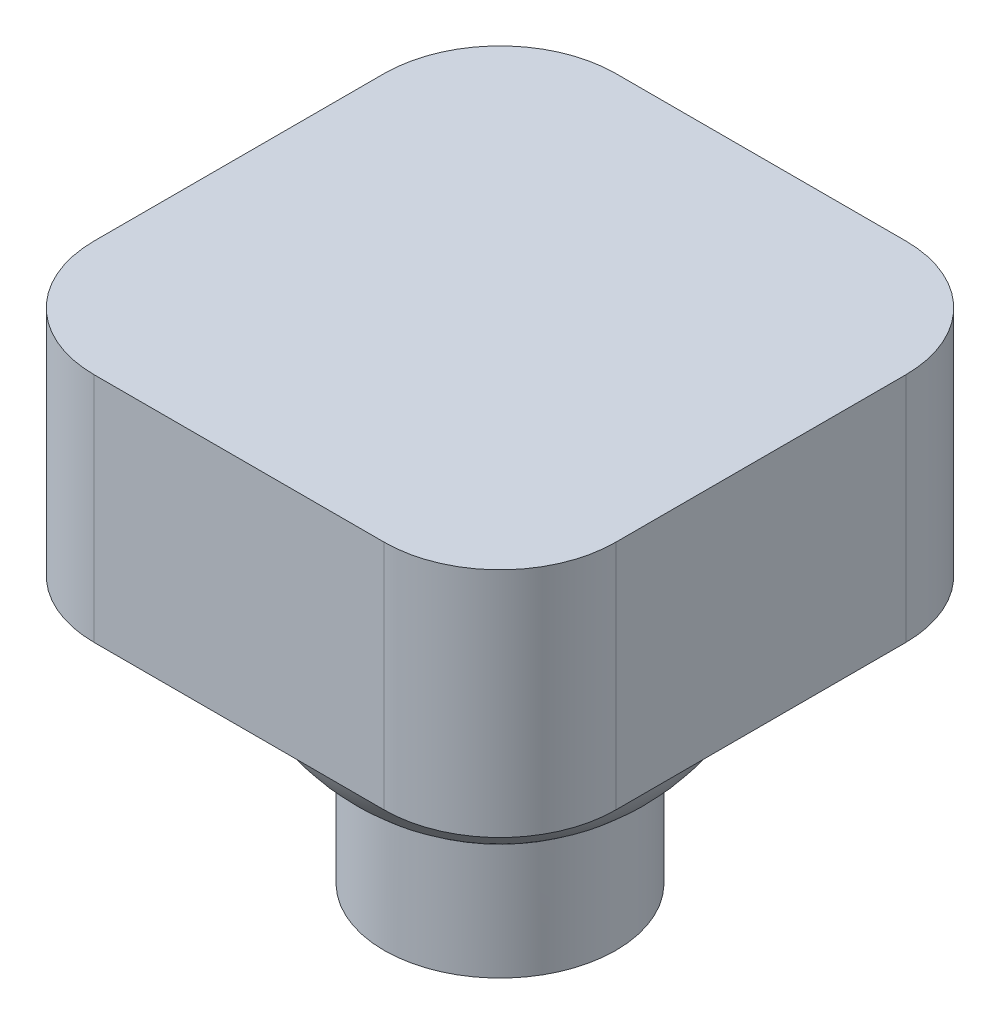
SolidWorks part; units mm, degrees
material "AISI 4340 Steel, normalized"
ref_plane "Front Plane" through (0, 0, 0) normal (0, 0, 1) x (1, 0, 0)
ref_plane "Top Plane" through (0, 0, 0) normal (0, 1, 0) x (1, 0, 0)
ref_plane "Right Plane" through (0, 0, 0) normal (1, 0, 0) x (0, 0, -1)
sketch "Sketch1" plane through (0, 0, 0) normal (0, 1, 0) x (1, 0, 0)
  circle A0 centre (0, 0) radius 25.4
  dimension "D1" = 50.8
extrude "Boss-Extrude1" add sketch "Sketch1" along normal blind 25.4
sketch "Sketch2" plane through (0, 0, 0) normal (0, 0, 1) x (1, 0, 0)
  line L0 (0, 145.4603) -> (0, 25.4)
  line L1 (25.4, 25.4) -> (-25.4, 25.4) construction
  line L2 (0, 25.4) -> (25.4, 25.4)
  line L3 (25.4, 0) -> (25.4, 25.4) construction
  circle A0 centre (0, 61.878) radius 44.45
  dimension "D1" = 88.9
revolve "Revolve1" add sketch "Sketch2" angle 360 about L0 region at (19.2927, 63.7197, 0)
ref_plane "Plane1" through (0, 58.42, 0) normal (0, 1, 0) x (1, 0, 0)
sketch "Sketch3" plane through (0, 58.42, 0) normal (0, 1, 0) x (1, 0, 0)
  line L1 (-57.15, 57.15) -> (57.15, 57.15)
  line L2 (-57.15, 57.15) -> (-57.15, -57.15)
  line L3 (-57.15, -57.15) -> (57.15, -57.15)
  line L4 (57.15, 57.15) -> (57.15, -57.15)
  circle A0 centre (0, 0) radius 44.45 construction
  point P5 (0, -57.15)
  point P7 (57.15, 0)
  point P10 (0, 44.45)
  point P11 (44.45, 0)
  dimension "D1" = 12.7
  dimension "D2" = 12.7
extrude "Boss-Extrude2" add sketch "Sketch3" along normal blind 50.8
fillet "Fillet1" radius 25.4 4 edges at (-57.15, 83.82, -57.15) (57.15, 83.82, -57.15) (57.15, 83.82, 57.15) (-57.15, 83.82, 57.15)
